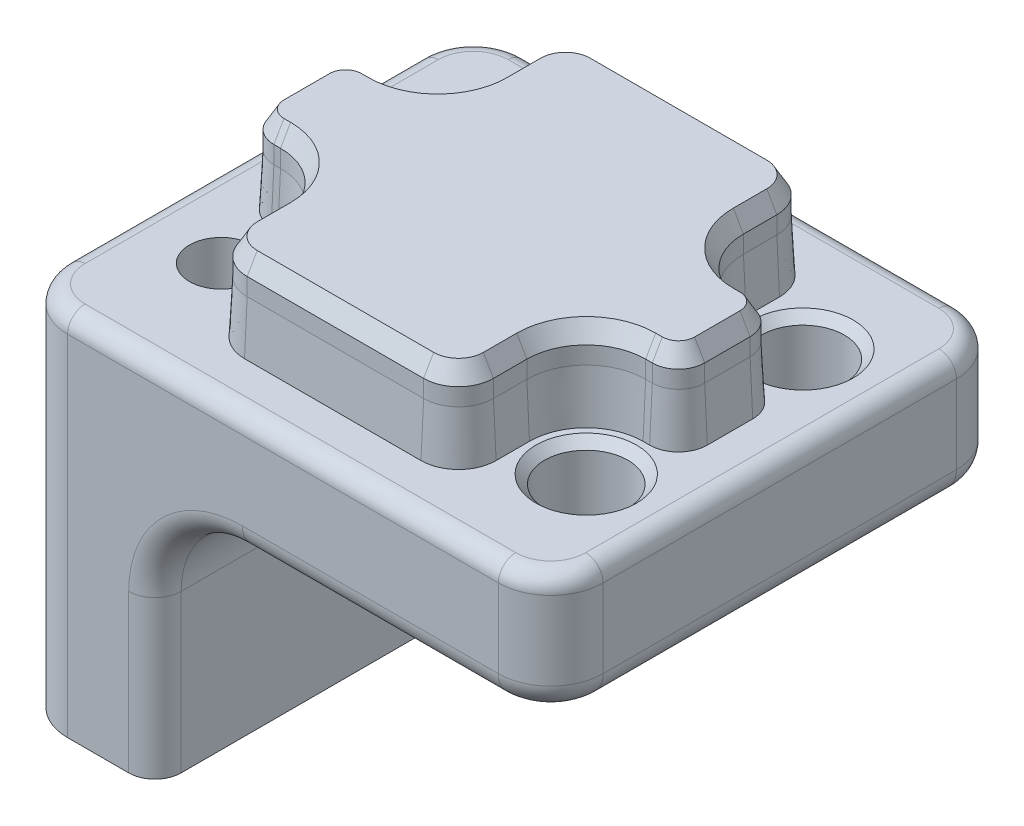
SolidWorks part; units mm, degrees
ref_plane "Front Plane" through (0, 0, 0) normal (0, 0, 1) x (1, 0, 0)
ref_plane "Top Plane" through (0, 0, 0) normal (0, 1, 0) x (1, 0, 0)
ref_plane "Right Plane" through (0, 0, 0) normal (1, 0, 0) x (0, 0, -1)
sketch "Sketch1" plane through (0, 0, 0) normal (0, 1, 0) x (1, 0, 0)
  line L0 (0, 23.7253) -> (0, -0.6764) construction
  line L1 (5.05, 10.11) -> (-5.05, 10.11)
  line L2 (-12.33, 1.3) -> (-12.33, -1.3)
  line L3 (-10.83, 2.8) -> (-10.45, 2.8)
  line L4 (-7.05, 8.11) -> (-7.05, 6.2)
  line L13 (-10.45, 6.2) -> (-7.05, 6.2) construction
  line L14 (-10.45, 6.2) -> (-10.45, 2.8) construction
  line L15 (-14.365, 0) -> (14.365, 0) construction
  line L16 (-10.45, -6.2) -> (-10.45, -2.8) construction
  line L17 (-10.45, -6.2) -> (-7.05, -6.2) construction
  line L18 (-7.05, -8.11) -> (-7.05, -6.2)
  line L19 (-10.83, -2.8) -> (-10.45, -2.8)
  line L20 (10.45, -6.2) -> (7.05, -6.2) construction
  line L21 (10.45, -6.2) -> (10.45, -2.8) construction
  line L22 (10.45, 6.2) -> (10.45, 2.8) construction
  line L23 (10.45, 6.2) -> (7.05, 6.2) construction
  line L24 (10.83, -2.8) -> (10.45, -2.8)
  line L25 (7.05, -8.11) -> (7.05, -6.2)
  line L26 (7.05, 8.11) -> (7.05, 6.2)
  line L27 (10.83, 2.8) -> (10.45, 2.8)
  line L28 (12.33, 1.3) -> (12.33, -1.3)
  line L29 (5.05, -10.11) -> (-5.05, -10.11)
  arc A0 (-10.45, 2.8) -> (-7.05, 6.2) centre (-10.45, 6.2) ccw
  arc A4 (-7.05, 8.11) -> (-5.05, 10.11) centre (-5.05, 8.11) cw
  arc A10 (-10.83, 2.8) -> (-12.33, 1.3) centre (-10.83, 1.3) ccw
  arc A11 (-10.83, -2.8) -> (-12.33, -1.3) centre (-10.83, -1.3) cw
  arc A12 (-7.05, -8.11) -> (-5.05, -10.11) centre (-5.05, -8.11) ccw
  arc A13 (-10.45, -2.8) -> (-7.05, -6.2) centre (-10.45, -6.2) cw
  arc A14 (10.45, -2.8) -> (7.05, -6.2) centre (10.45, -6.2) ccw
  arc A15 (7.05, -8.11) -> (5.05, -10.11) centre (5.05, -8.11) cw
  arc A16 (10.83, -2.8) -> (12.33, -1.3) centre (10.83, -1.3) ccw
  arc A17 (10.83, 2.8) -> (12.33, 1.3) centre (10.83, 1.3) cw
  arc A18 (7.05, 8.11) -> (5.05, 10.11) centre (5.05, 8.11) ccw
  arc A19 (10.45, 2.8) -> (7.05, 6.2) centre (10.45, 6.2) cw
  point P11 (0, 0)
  point P18 (0, 10.11)
  point P29 (-12.33, 0)
  point P47 (12.33, 0)
  dimension "D2" = 3.4
  dimension "D4" = 2
  dimension "D5" = 6.2
  dimension "D9" = 1.5
  dimension "D1" = 10.45
  dimension "D3" = 12.33
  dimension "D6" = 10.11
  dimension "D7" = 5.05
  dimension "D8" = 1.88
extrude "Boss-Extrude1" add sketch "Sketch1" along normal blind 5
sketch "Sketch2" plane through (0, 0, 0) normal (0, -1, 0) x (1, 0, 0)
  line L0 (5.05, 10.11) -> (-5.05, 10.11) construction
  line L1 (15.33, -13.11) -> (-15.33, -13.11)
  line L2 (15.33, -13.11) -> (15.33, 13.11)
  line L3 (15.33, 13.11) -> (-15.33, 13.11)
  line L4 (-15.33, -13.11) -> (-15.33, 13.11)
  line L5 (15.33, -13.11) -> (-15.33, 13.11) construction
  line L6 (15.33, 13.11) -> (-15.33, -13.11) construction
  line L7 (-12.33, -1.3) -> (-12.33, 1.3) construction
  point P0 (0, 0)
  dimension "D1" = 3
  dimension "D2" = 3
extrude "Boss-Extrude2" add sketch "Sketch2" along normal blind 7
sketch "Sketch7" plane through (0, 0, 13.11) normal (0, 0, 1) x (1, 0, 0)
  line L1 (15.33, -7) -> (-15.33, -7) construction
  line L2 (-7.33, -21) -> (-15.33, -21)
  line L3 (-15.33, -21) -> (-15.33, -7)
  line L4 (-15.33, -7) -> (-7.33, -7)
  line L7 (-7.33, -7) -> (-7.33, -21)
  point P4 (0, 0)
  dimension "D2" = 14
  dimension "D3" = 8
extrude "Boss-Extrude3" add sketch "Sketch7" against normal up to surface (26.22 mm away) up to face at (0, -3.5, -13.11)
sketch "Sketch3" plane through (0, -7, 0) normal (0, -1, 0) x (1, 0, 0)
  circle A0 centre (10.45, 6.2) radius 2.3813
  circle A1 centre (10.45, -6.2) radius 2.3813
  circle A2 centre (-10.45, -6.2) radius 1.815
  circle A3 centre (-10.45, 6.2) radius 1.815
  dimension "D1" = 3.63
  dimension "D2" = 4.7625
extrude "Cut-Extrude1" cut sketch "Sketch3" against normal through all both and the other way through all
fillet "Fillet1" radius 3 4 edges at (15.33, -3.5, -13.11) (15.33, -3.5, 13.11) (-15.33, -10.5, -13.11) (-15.33, -10.5, 13.11)
chamfer "Chamfer1" distance 1 angle 30 24 edges at (8.0458, 5, -3.7958) (7.05, 5, -7.155) (10.64, 5, -2.8) (6.4642, 5, -9.5242) (11.8907, 5, -2.3607) (0, 5, -10.11) (12.33, 5, 0) (-6.4642, 5, -9.5242) (11.8907, 5, 2.3607) (-7.05, 5, -7.155) (10.64, 5, 2.8) (-8.0458, 5, -3.7958) (8.0458, 5, 3.7958) (-10.64, 5, -2.8) (7.05, 5, 7.155) (-11.8907, 5, -2.3607) (6.4642, 5, 9.5242) (-12.33, 5, 0) (0, 5, 10.11) (-11.8907, 5, 2.3607) (-6.4642, 5, 9.5242) (-10.64, 5, 2.8) (-7.05, 5, 7.155) (-8.0458, 5, 3.7958) first distance on face at (8.3979, 2.5, -4.1479) first distance on face at (7.05, 2.5, -7.155) first distance on face at (10.64, 2.5, -2.8) first distance on face at (6.2571, 2.5, -9.3171) first distance on face at (11.7353, 2.5, -2.2053) first distance on face at (0, 2.5, -10.11) first distance on face at (12.33, 2.5, 0) first distance on face at (-6.2571, 2.5, -9.3171) first distance on face at (11.7353, 2.5, 2.2053) first distance on face at (-7.05, 2.5, -7.155) first distance on face at (10.64, 2.5, 2.8) first distance on face at (-8.3979, 2.5, -4.1479) first distance on face at (8.3979, 2.5, 4.1479) first distance on face at (-10.64, 2.5, -2.8) first distance on face at (7.05, 2.5, 7.155) first distance on face at (-11.7353, 2.5, -2.2053) first distance on face at (6.2571, 2.5, 9.3171) first distance on face at (-12.33, 2.5, 0) first distance on face at (0, 2.5, 10.11) first distance on face at (-11.7353, 2.5, 2.2053) first distance on face at (-6.2571, 2.5, 9.3171) first distance on face at (-10.64, 2.5, 2.8) first distance on face at (-7.05, 2.5, 7.155) first distance on face at (-8.3979, 2.5, 4.1479)
chamfer "Chamfer3" distance 0.5 angle 45 4 edges at (10.45, 0, 3.8187) (10.45, 0, -8.5812) (10.45, -7, -8.5812) (10.45, -7, 3.8187)
fillet "Fillet3" radius 1 8 edges at (-14.4513, 0, -12.2313) (-15.33, 0, 0) (-14.4513, 0, 12.2313) (0, 0, 13.11) (14.4513, 0, 12.2313) (15.33, 0, 0) (14.4513, 0, -12.2313) (0, 0, -13.11)
chamfer "Chamfer4" distance 0.15 distance2 3 24 edges at (11.8907, 0, -2.3607) (12.33, 0, 0) (11.8907, 0, 2.3607) (-6.4642, 0, -9.5242) (-7.05, 0, -7.155) (0, 0, -10.11) (-8.0458, 0, -3.7958) (6.4642, 0, -9.5242) (-10.64, 0, -2.8) (7.05, 0, -7.155) (-11.8907, 0, -2.3607) (8.0458, 0, -3.7958) (-12.33, 0, 0) (10.64, 0, -2.8) (-11.8907, 0, 2.3607) (-10.64, 0, 2.8) (-8.0458, 0, 3.7958) (-7.05, 0, 7.155) (10.64, 0, 2.8) (-6.4642, 0, 9.5242) (8.0458, 0, 3.7958) (7.05, 0, 7.155) (6.4642, 0, 9.5242) (0, 0, 10.11) first distance on face at (0, 0, 0)
fillet "Fillet4" radius 5 1 edges at (-7.33, -7, 0)
fillet "Fillet5" radius 1.5 9 edges at (-7.33, -16.5, 13.11) (-5.8655, -8.4645, 13.11) (5, -7, 13.11) (14.4513, -7, 12.2313) (15.33, -7, 0) (14.4513, -7, -12.2313) (5, -7, -13.11) (-5.8655, -8.4645, -13.11) (-7.33, -16.5, -13.11)
chamfer "Chamfer5" distance 0.75 angle 45 2 edges at (-10.45, -21, -8.015) (-10.45, -21, 4.385)
